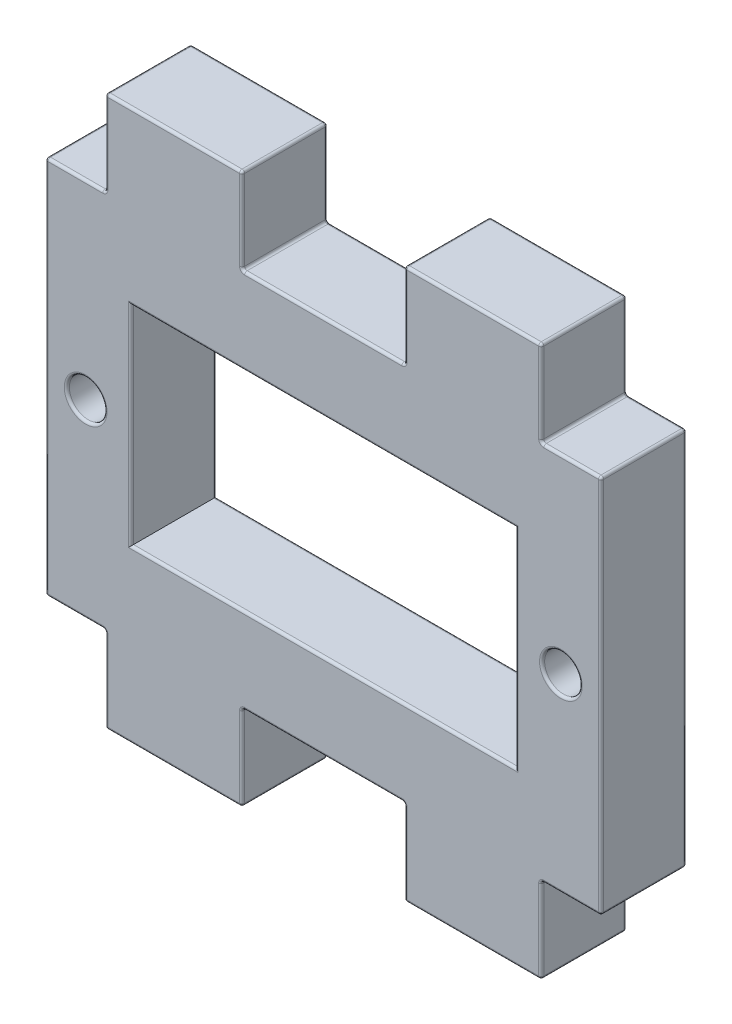
SolidWorks part; units mm, degrees
ref_plane "Płaszczyzna przednia" through (0, 0, 0) normal (0, 0, 1) x (1, 0, 0)
ref_plane "Płaszczyzna górna" through (0, 0, 0) normal (0, 1, 0) x (1, 0, 0)
ref_plane "Płaszczyzna prawa" through (0, 0, 0) normal (1, 0, 0) x (0, 0, -1)
sketch "Szkic1" plane through (0, 0, 0) normal (0, 0, 1) x (1, 0, 0)
  line L0 (-16.25, 11.1) -> (16.25, 11.1)
  line L1 (-11.25, -6.1) -> (11.25, -6.1)
  line L2 (-11.25, -6.1) -> (-11.25, 6.1)
  line L3 (-11.25, 6.1) -> (11.25, 6.1)
  line L4 (11.25, -6.1) -> (11.25, 6.1)
  line L5 (-11.25, -6.1) -> (11.25, 6.1) construction
  line L6 (-11.25, 6.1) -> (11.25, -6.1) construction
  line L7 (16.25, -11.1) -> (16.25, 11.1)
  line L8 (-16.25, -11.1) -> (16.25, -11.1)
  line L9 (-16.25, -11.1) -> (-16.25, 11.1)
  line L10 (0, 0) -> (0, 6.1) construction
  line L11 (-12.75, 11.1) -> (-4.75, 11.1)
  line L12 (-12.75, 11.1) -> (-12.75, 16.1)
  line L13 (-12.75, 16.1) -> (-4.75, 16.1)
  line L14 (-4.75, 11.1) -> (-4.75, 16.1)
  line L15 (0, 0) -> (-16.25, 0) construction
  line L16 (4.75, 11.1) -> (4.75, 16.1)
  line L17 (12.75, 16.1) -> (4.75, 16.1)
  line L18 (12.75, 11.1) -> (12.75, 16.1)
  line L19 (12.75, -11.1) -> (12.75, -16.1)
  line L20 (12.75, -16.1) -> (4.75, -16.1)
  line L21 (4.75, -11.1) -> (4.75, -16.1)
  line L22 (-4.75, -11.1) -> (-4.75, -16.1)
  line L23 (-12.75, -16.1) -> (-4.75, -16.1)
  line L24 (-12.75, -11.1) -> (-12.75, -16.1)
  circle A0 centre (-13.9, 0) radius 1.1
  circle A1 centre (13.9, 0) radius 1.1
  point P0 (0, 0)
  dimension "D7" = 2.2
  dimension "D1" = 12.2
  dimension "D2" = 22.5
  dimension "D4" = 3.5
  dimension "D5" = 5
  dimension "D6" = 8
  dimension "D8" = 2.65
  dimension "D3" = 5
extrude "Dodanie-wyciągnięcie1" add sketch "Szkic1" along normal mid plane 5 contours L9 L8 L7 L0 L4 L1 L2 L3 A0 A1 | L8 L24 L23 L22 | L8 L21 L20 L19 | L0 L18 L17 L16 | L0 L14 L13 L12 region at (-14.5, 10.7064, 0) region at (-8.75, 13.6, 0) region at (-8.75, -13.6, 0) region at (8.75, 13.6, 0) region at (8.75, -13.6, 0)
fillet "Zaokrąglenie1" radius 0.15 60 edges at (-12.75, 16.1, 0) (-8.75, 16.1, -2.5) (-12.75, 13.6, -2.5) (-8.75, 16.1, 2.5) (-4.75, 16.1, 0) (-12.75, 13.6, 2.5) (-12.75, 11.1, 0) (-4.75, 13.6, -2.5) (-14.5, 11.1, -2.5) (-4.75, 13.6, 2.5) (-4.75, 11.1, 0) (-14.5, 11.1, 2.5) (-16.25, 11.1, 0) (0, 11.1, -2.5) (-16.25, 0, -2.5) (0, 11.1, 2.5) (4.75, 11.1, 0) (-16.25, 0, 2.5) (-16.25, -11.1, 0) (4.75, 13.6, -2.5) (-14.5, -11.1, -2.5) (4.75, 13.6, 2.5) (4.75, 16.1, 0) (-12.75, -11.1, 0) (-14.5, -11.1, 2.5) (8.75, 16.1, -2.5) (-12.75, -13.6, -2.5) (12.75, 16.1, 0) (8.75, 16.1, 2.5) (-12.75, -16.1, 0) (-12.75, -13.6, 2.5) (12.75, 13.6, -2.5) (-8.75, -16.1, -2.5) (12.75, 13.6, 2.5) (12.75, 11.1, 0) (-4.75, -16.1, 0) (-8.75, -16.1, 2.5) (14.5, 11.1, -2.5) (-4.75, -13.6, -2.5) (14.5, 11.1, 2.5) (16.25, 11.1, 0) (-4.75, -13.6, 2.5) (-4.75, -11.1, 0) (16.25, 0, -2.5) (0, -11.1, -2.5) (16.25, -11.1, 0) (16.25, 0, 2.5) (4.75, -11.1, 0) (0, -11.1, 2.5) (14.5, -11.1, -2.5) (4.75, -13.6, -2.5) (14.5, -11.1, 2.5) (12.75, -11.1, 0) (4.75, -16.1, 0) (4.75, -13.6, 2.5) (12.75, -13.6, -2.5) (8.75, -16.1, -2.5) (12.75, -13.6, 2.5) (8.75, -16.1, 2.5) (12.75, -16.1, 0)
fillet "Zaokrąglenie2" radius 0.15 12 edges at (15, 0, -2.5) (-12.8, 0, -2.5) (0, -6.1, -2.5) (-11.25, 0, -2.5) (0, 6.1, -2.5) (11.25, 0, -2.5) (0, 6.1, 2.5) (-11.25, 0, 2.5) (0, -6.1, 2.5) (11.25, 0, 2.5) (-12.8, 0, 2.5) (15, 0, 2.5)
